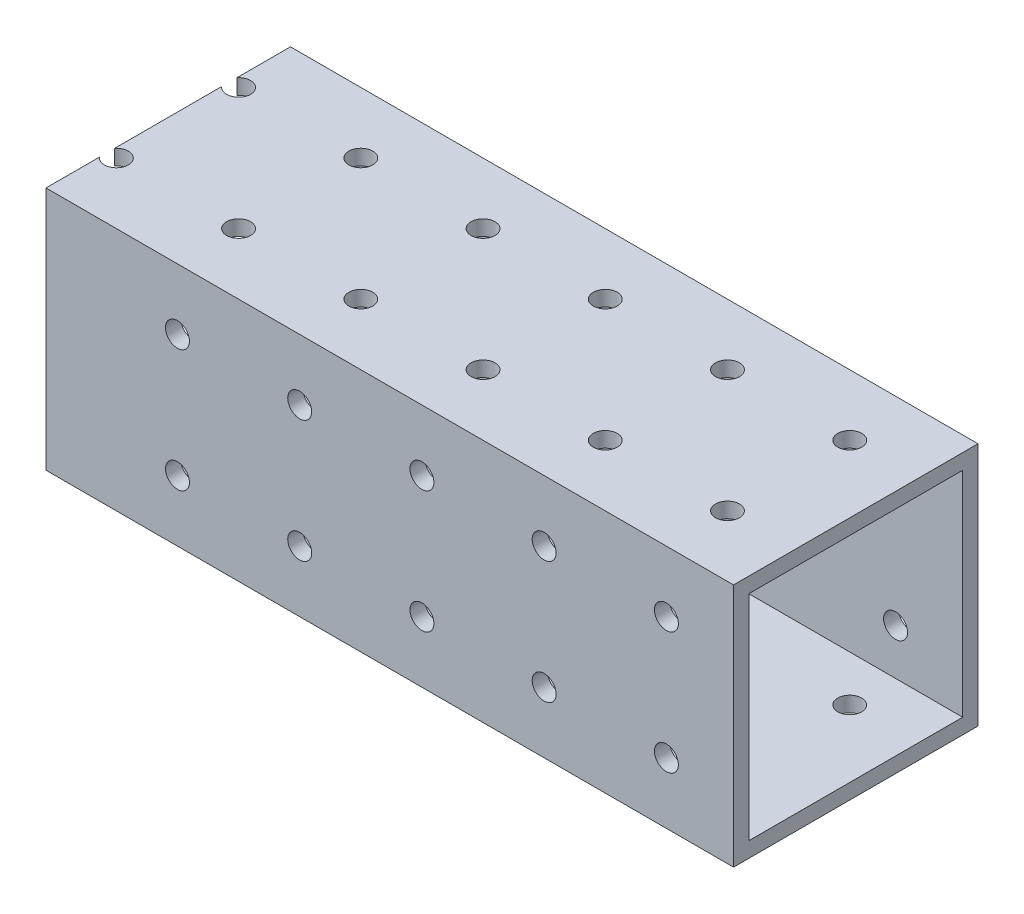
SolidWorks part; units mm, degrees
material "6061-T6 (SS)"
ref_plane "Front Plane" through (0, 0, 0) normal (0, 0, 1) x (1, 0, 0)
ref_plane "Top Plane" through (0, 0, 0) normal (0, 1, 0) x (1, 0, 0)
ref_plane "Right Plane" through (0, 0, 0) normal (1, 0, 0) x (0, 0, -1)
sketch "Sketch1" plane through (0, 0, 0) normal (1, 0, 0) x (0, 0, -1)
  line L1 (0, 0) -> (50.8, 0)
  line L2 (0, 0) -> (0, 50.8)
  line L3 (0, 50.8) -> (50.8, 50.8)
  line L4 (50.8, 0) -> (50.8, 50.8)
  dimension "D1" = 50.8
extrude "Boss-Extrude1" add sketch "Sketch1" along normal blind 142.875
shell "Shell1" thickness 3.175 removed face at (0, 25.4, -25.4) removed face at (142.875, 25.4, -25.4)
sketch "Sketch2" plane through (0, 0, -50.8) normal (0, 0, -1) x (-1, 0, 0)
  circle A1 centre (-103.5208, 38.1) radius 2.4892 construction
  circle A2 centre (-78.1208, 38.1) radius 2.4892 construction
  circle A3 centre (-52.7208, 38.1) radius 2.4892 construction
  circle A4 centre (-27.3208, 38.1) radius 2.4892 construction
  circle A5 centre (-27.3208, 12.7) radius 2.4892 construction
  circle A6 centre (-52.7208, 12.7) radius 2.4892 construction
  circle A7 centre (-78.1208, 12.7) radius 2.4892 construction
  circle A8 centre (-103.5208, 12.7) radius 2.4892 construction
  circle A10 centre (-128.9208, 38.1) radius 2.4892
  circle A11 centre (-103.5208, 38.1) radius 2.4892
  circle A12 centre (-78.1208, 38.1) radius 2.4892
  circle A13 centre (-52.7208, 38.1) radius 2.4892
  circle A14 centre (-27.3208, 38.1) radius 2.4892
  circle A15 centre (-27.3208, 12.7) radius 2.4892
  circle A16 centre (-52.7208, 12.7) radius 2.4892
  circle A17 centre (-78.1208, 12.7) radius 2.4892
  circle A18 centre (-103.5208, 12.7) radius 2.4892
  circle A19 centre (-128.9208, 12.7) radius 2.4892
  dimension "D1" = 25.4
  dimension "D2" = 25.4
extrude "Cut-Extrude1" cut sketch "Sketch2" against normal through all
sketch "Sketch3" plane through (0, 0, 0) normal (0, -1, 0) x (1, 0, 0)
  line L1 (128.9208, -38.1) -> (128.9208, -12.7) construction
  line L2 (128.9208, -12.7) -> (128.9208, 12.7) construction
  line L3 (287.6708, 0) -> (-309.2292, 0) construction
  line L4 (142.875, -50.8) -> (0, -50.8) construction
  circle A0 centre (128.9208, -12.7) radius 2.4892
  circle A1 centre (128.9208, -38.1) radius 2.4892
  dimension "D1" = 4.9784
  dimension "D2" = 12.7
  dimension "D3" = 12.7
extrude "Cut-Extrude2" cut sketch "Sketch3" against normal through all
pattern_linear "LPattern1" count 6 spacing 25.4 along (-1, 0, 0) of "Cut-Extrude2"
